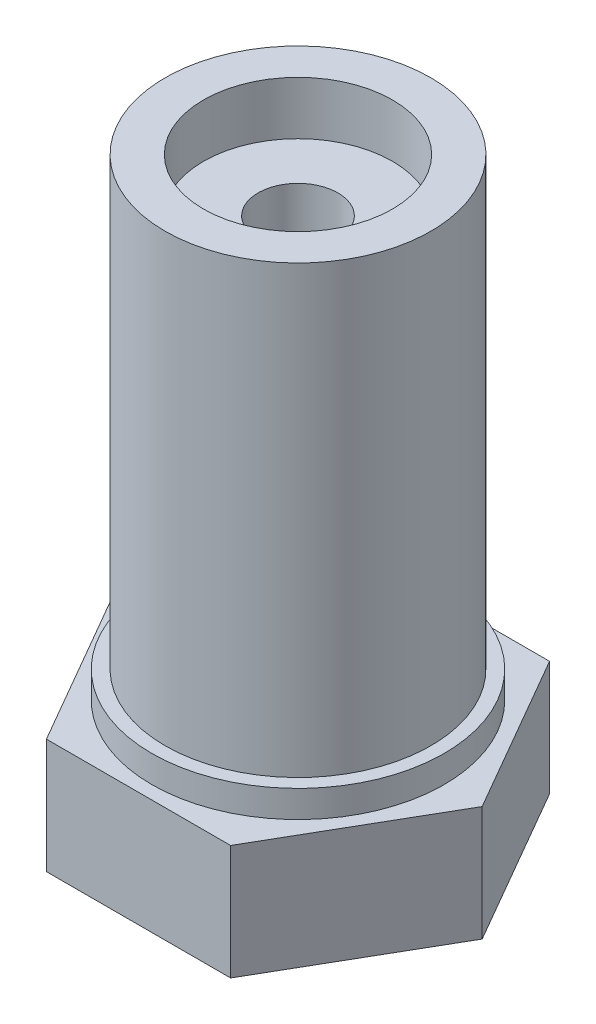
SolidWorks part; units mm, degrees
ref_plane "Front Plane" through (0, 0, 0) normal (0, 0, 1) x (1, 0, 0)
ref_plane "Top Plane" through (0, 0, 0) normal (0, 1, 0) x (1, 0, 0)
ref_plane "Right Plane" through (0, 0, 0) normal (1, 0, 0) x (0, 0, -1)
sketch "Sketch1" plane through (0, 0, 0) normal (0, 1, 0) x (1, 0, 0)
  line L1 (3.4641, 6) -> (-3.4641, 6)
  line L2 (-3.4641, 6) -> (-6.9282, 0)
  line L3 (-6.9282, 0) -> (-3.4641, -6)
  line L4 (-3.4641, -6) -> (3.4641, -6)
  line L5 (3.4641, -6) -> (6.9282, 0)
  line L6 (6.9282, 0) -> (3.4641, 6)
  circle A0 centre (0, 0) radius 6 construction
  dimension "D1" = 12
extrude "Boss-Extrude1" add sketch "Sketch1" along normal blind 4.318
sketch "Sketch2" plane through (0, 4.318, 0) normal (0, 1, 0) x (1, 0, 0)
  circle A0 centre (0, 0) radius 5
  circle A1 centre (0, 0) radius 5.5
  dimension "D1" = 11
  dimension "D2" = 10
extrude "Boss-Extrude2" add sketch "Sketch2" along normal blind 1.016
extrude "Boss-Extrude3" add sketch "Sketch2<2>" along normal blind 17.78 contours A0 region at (0, 4.318, 0)
sketch "Sketch2<2>" plane through (0, 4.318, 0) normal (0, 1, 0) x (1, 0, 0) same geometry as "Sketch2"
sketch "Sketch4" plane through (0, 22.098, 0) normal (0, 1, 0) x (1, 0, 0)
  circle A0 centre (0, 0) radius 3.556
  circle A1 centre (0, 0) radius 1.5
  dimension "D1" = 7.112
  dimension "D2" = 3
extrude "Cut-Extrude2" cut sketch "Sketch4" against normal through all contours A1 region at (0, 22.098, 0)
extrude "Cut-Extrude3" cut sketch "Sketch4<3>" against normal blind 2
sketch "Sketch4<3>" plane through (0, 22.098, 0) normal (0, 1, 0) x (1, 0, 0) same geometry as "Sketch4"
